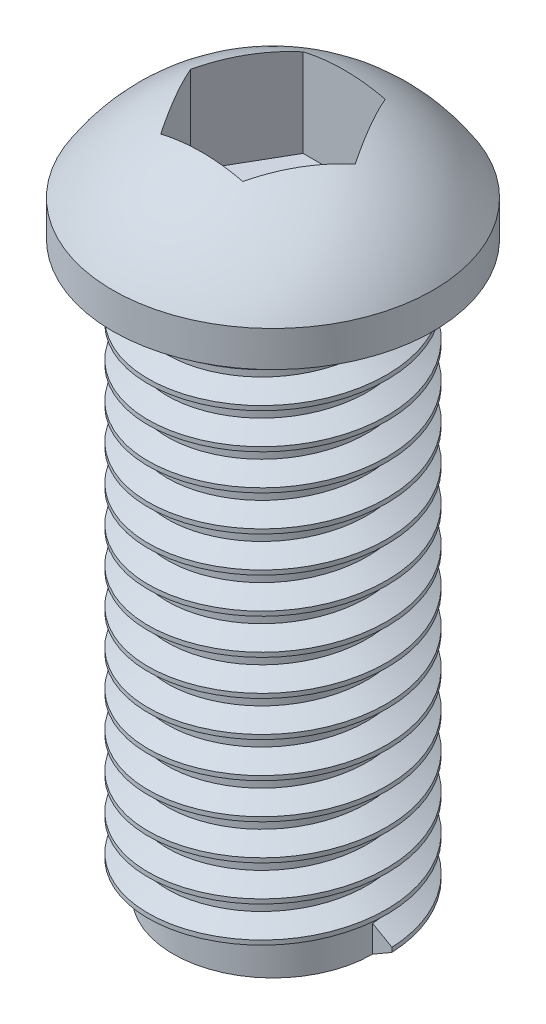
SolidWorks part; units mm, degrees
ref_plane "Front Plane" through (0, 0, 0) normal (0, 0, 1) x (1, 0, 0)
ref_plane "Top Plane" through (0, 0, 0) normal (0, 1, 0) x (1, 0, 0)
ref_plane "Right Plane" through (0, 0, 0) normal (1, 0, 0) x (0, 0, -1)
sketch "Sketch1" plane through (0, 0, 0) normal (0, 1, 0) x (1, 0, 0)
  circle A0 centre (0, 0) radius 1.4
  dimension "D1" = 2.8
extrude "Boss-Extrude1" add sketch "Sketch1" against normal blind 8
sketch "Sketch2" plane through (0, 0, 0) normal (0, 0, 1) x (1, 0, 0)
  line L0 (0, 0) -> (2.25, 0)
  line L1 (2.25, 0) -> (2.25, 0.5)
  line L2 (0, 0) -> (0, 1.75)
  arc A0 (0, 1.75) -> (2.25, 0.5) centre (0, -0.9) cw
  dimension "D1" = 2.25
  dimension "D2" = 0.5
  dimension "D3" = 1.75
revolve "Revolve1" add sketch "Sketch2" angle 360 about L2
sketch "Sketch3" plane through (0, 0, 0) normal (0, 1, 0) x (1, 0, 0)
  line L1 (1.1547, 0) -> (0.5774, 1)
  line L2 (0.5774, 1) -> (-0.5774, 1)
  line L3 (-0.5774, 1) -> (-1.1547, 0)
  line L4 (-1.1547, 0) -> (-0.5774, -1)
  line L5 (-0.5774, -1) -> (0.5774, -1)
  line L6 (0.5774, -1) -> (1.1547, 0)
  circle A0 centre (0, 0) radius 1 construction
  dimension "D1" = 2
  dimension "D2" = 1
extrude "Cut-Extrude1" cut sketch "Sketch3" against normal blind 1.5 from offset 1.75
thread "Thread2" pitch 0.5 method extrude profile "Thread Profile2" start angle 0, offset 0, length 0, pitch 0.5, diameter 2.8
ref_plane "Plane2" through (1.4, -8, 0) normal (0, 0, 1) x (1, 0, 0)
sketch "Thread Profile2" plane through (1.4, -8, 0) normal (0, 0, 1) x (1, 0, 0)
  line L0 (0, 0) -> (0, 0.5) construction
  line L1 (0, 0) -> (0.2706, 0.1562)
  line L2 (0.2706, 0.1562) -> (0.2706, 0.2187)
  line L3 (0.2706, 0.2187) -> (0, 0.375)
  line L4 (0.2706, 0.1875) -> (0, 0.1875) construction
  line L11 (0, 0) -> (0, 0.375)
  point P2 (0, 0)
  dimension "Pitch" = 0.5
  dimension "Profile_Angle" = 60
  dimension "Profile_Land" = 0.0625
  dimension "Profile_Height" = 0.2706
